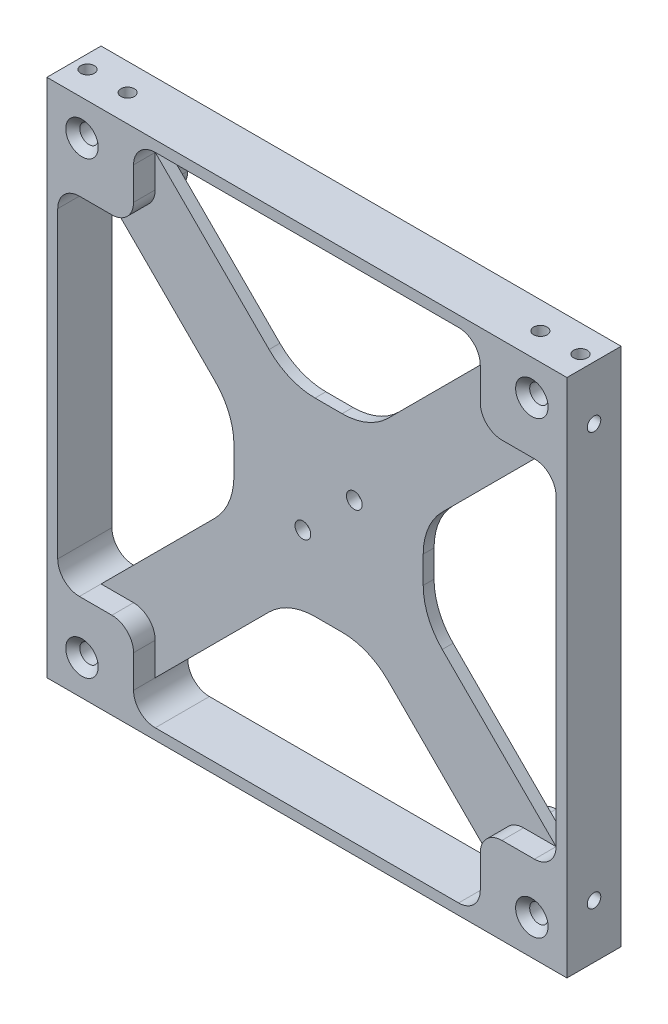
SolidWorks part; units mm, degrees
material "7075-T6 (SN)"
ref_plane "Front Plane" through (0, 0, 0) normal (0, 0, 1) x (1, 0, 0)
ref_plane "Top Plane" through (0, 0, 0) normal (0, 1, 0) x (1, 0, 0)
ref_plane "Right Plane" through (0, 0, 0) normal (1, 0, 0) x (0, 0, -1)
sketch "Construction Lines" plane through (0, 0, 0) normal (0, 0, 1) x (1, 0, 0)
  line L0 (0, 0) -> (0, -14.7163) construction
  line L1 (0, 0) -> (23.9312, 0) construction
sketch "Sketch3" plane through (0, 0, 0) normal (0, 0, 1) x (1, 0, 0)
  line L0 (0, 48) -> (48, 48)
  line L1 (0, 200000) -> (0, -200014.7163) construction
  line L2 (48, 48) -> (48, 0)
  line L3 (-200000, 0) -> (200023.9312, 0) construction
  line L4 (0, 46) -> (28, 46)
  line L5 (46, 28) -> (46, 0)
  line L6 (0, 48) -> (0, 46)
  line L7 (48, 0) -> (46, 0)
  line L8 (32, 42) -> (32, 36)
  line L9 (36, 32) -> (42, 32)
  line L11 (0, 46) -> (46, 46) construction
  line L12 (46, 46) -> (46, 0) construction
  arc A0 (28, 46) -> (32, 42) centre (28, 42) cw
  arc A1 (32, 36) -> (36, 32) centre (36, 36) ccw
  arc A2 (46, 28) -> (42, 32) centre (42, 28) ccw
  dimension "D6" = 4
  dimension "D1" = 48
  dimension "D2" = 48
  dimension "D4" = 16
  dimension "D5" = 16
  dimension "D3" = 2
extrude "BottomLayer" add sketch "Sketch3" along normal blind 4
sketch "TopHolePosition" plane through (0, 0, 4) normal (0, 0, 1) x (1, 0, 0)
  line L0 (0, 0) -> (48, 48) construction
sketch "Sketch6" plane through (0, 0, 4) normal (0, 0, 1) x (1, 0, 0)
  line L0 (0, 17.4706) -> (0, 0)
  line L1 (0, 0) -> (17.4706, 0)
  line L3 (0, 17.4706) -> (2.5, 17.4706)
  line L4 (0, 0) -> (48, 48) construction
  line L6 (17.4706, 0) -> (17.4706, 2.5)
  line L7 (38, 48) -> (10.9853, 20.9853)
  line L8 (48, 38) -> (20.9853, 10.9853)
  line L15 (48, 48) -> (0, 48) construction
  line L16 (48, 0) -> (48, 48) construction
  line L17 (38, 48) -> (48, 48)
  line L18 (48, 48) -> (48, 38)
  arc A1 (20.9853, 10.9853) -> (17.4706, 2.5) centre (29.4706, 2.5) ccw
  arc A2 (10.9853, 20.9853) -> (2.5, 17.4706) centre (2.5, 29.4706) cw
  dimension "D1" = 2.5
  dimension "D2" = 2.5
  dimension "D4" = 12
extrude "MiddleLayer" add sketch "Sketch6" along normal blind 2
sketch "Sketch10" plane through (0, 0, 6) normal (0, 0, 1) x (1, 0, 0)
  line L8 (48, 48) -> (0, 48)
  line L9 (48, 0) -> (48, 48)
  line L10 (46, 0) -> (48, 0)
  line L11 (46, 28) -> (46, 0)
  line L12 (36, 32) -> (42, 32)
  line L13 (32, 42) -> (32, 36)
  line L14 (0, 46) -> (28, 46)
  line L15 (0, 48) -> (0, 46)
  line L16 (48, 48) -> (0, 48)
  line L17 (48, 0) -> (48, 48)
  line L18 (46, 0) -> (48, 0)
  line L19 (46, 28) -> (46, 0)
  line L20 (36, 32) -> (42, 32)
  line L21 (32, 42) -> (32, 36)
  line L22 (0, 46) -> (28, 46)
  line L23 (0, 48) -> (0, 46)
  arc A3 (46, 28) -> (42, 32) centre (42, 28) ccw
  arc A4 (46, 28) -> (42, 32) centre (42, 28) ccw
  arc A5 (32, 36) -> (36, 32) centre (36, 36) ccw
  arc A6 (32, 36) -> (36, 32) centre (36, 36) ccw
  arc A7 (32, 42) -> (28, 46) centre (28, 42) ccw
  arc A8 (32, 42) -> (28, 46) centre (28, 42) ccw
  dimension "D1" = 0
extrude "FillUpLayer" add sketch "Sketch10" against normal blind 2
sketch "Sketch11" plane through (0, 0, 6) normal (0, 0, 1) x (1, 0, 0)
  line L8 (48, 48) -> (0, 48)
  line L9 (48, 0) -> (48, 48)
  line L10 (46, 0) -> (48, 0)
  line L11 (46, 28) -> (46, 0)
  line L12 (36, 32) -> (42, 32)
  line L13 (32, 42) -> (32, 36)
  line L14 (0, 46) -> (28, 46)
  line L15 (0, 48) -> (0, 46)
  line L16 (48, 48) -> (0, 48)
  line L17 (48, 0) -> (48, 48)
  line L18 (46, 0) -> (48, 0)
  line L19 (46, 28) -> (46, 0)
  line L20 (36, 32) -> (42, 32)
  line L21 (32, 42) -> (32, 36)
  line L22 (0, 46) -> (28, 46)
  line L23 (0, 48) -> (0, 46)
  arc A3 (46, 28) -> (42, 32) centre (42, 28) ccw
  arc A4 (46, 28) -> (42, 32) centre (42, 28) ccw
  arc A5 (32, 36) -> (36, 32) centre (36, 36) ccw
  arc A6 (32, 36) -> (36, 32) centre (36, 36) ccw
  arc A7 (32, 42) -> (28, 46) centre (28, 42) ccw
  arc A8 (32, 42) -> (28, 46) centre (28, 42) ccw
  dimension "D1" = 0
extrude "TopLayer" add sketch "Sketch11" along normal blind 4
sketch "HolePosition" plane through (0, 0, 10) normal (0, 0, 1) x (1, 0, 0)
  line L0 (0, 41.525) -> (41.525, 41.525) construction
  line L1 (0, 200000) -> (0, -200014.7163) construction
  line L2 (0, 0) -> (48, 48) construction
  line L3 (41.525, 41.525) -> (41.525, 0) construction
  line L4 (-200000, 0) -> (200023.9312, 0) construction
  dimension "D1" = 41.525
hole_wizard "M3 Clearance Hole1" positions "Sketch13" profile "Sketch14" hole size "M3" standard "ISO" end condition through all
sketch "Sketch13" plane through (0, 0, 10) normal (0, 0, 1) x (1, 0, 0)
  point P0 (41.525, 41.525)
sketch "Sketch14" plane through (41.525, 41.525, 10) normal (1, 0, 0) x (0, -1, 0)
  line L0 (0, 0) -> (0, 10)
  line L1 (0, 10) -> (1.7, 10)
  line L2 (1.7, 10) -> (1.7, 1.3)
  line L3 (1.7, 1.3) -> (3, 0)
  line L5 (3, 0) -> (0, 0)
  line L6 (-1.7, 1.3) -> (-3, 0) construction
  line L11 (0, -6.35) -> (0, 107.95) construction
  dimension "Thru Hole Dia." = 3.4
  dimension "Thru Hole Depth" = 10
  dimension "Near C'Sink Dia." = 6
  dimension "Near C'Sink Angle" = 90
ref_axis "Axis1" through (0, 0, -0.5) along (0, 0, 1)
sketch "M2HolePositions" plane through (0, 0, 6) normal (0, 0, 1) x (1, 0, 0)
  line L0 (0, 0) -> (48, 48) construction
  line L1 (0, 200000) -> (0, -200014.7163) construction
  line L2 (0, 0) -> (6.9513, -6.9513) construction
  line L3 (-200000, 0) -> (200023.9312, 0) construction
  line L4 (0, 4.75) -> (4.75, 4.75) construction
  line L5 (4.75, 4.75) -> (4.75, 0) construction
  dimension "D1" = 45
  dimension "D3" = 4.75
hole_wizard "M2.5 Clearance Hole1" positions "Sketch24" profile "Sketch25" hole size "M2.5" standard "ISO" end condition through all
sketch "Sketch24" plane through (0, 0, 6) normal (0, 0, 1) x (1, 0, 0)
  point P0 (4.75, 4.75)
sketch "Sketch25" plane through (4.75, 4.75, 6) normal (1, 0, 0) x (0, -1, 0)
  line L0 (0, 0) -> (0, 6)
  line L1 (0, 6) -> (1.45, 6)
  line L2 (1.45, 6) -> (1.45, 0)
  line L5 (1.45, 0) -> (0, 0)
  line L11 (0, -6.35) -> (0, 107.95) construction
  dimension "Thru Hole Dia." = 2.9
  dimension "Thru Hole Depth" = 6
pattern_circular "CirPattern1" count 4 every 90 about axis through (0, 0, -0.5) along (0, 0, 1) of "TopLayer", "FillUpLayer", "MiddleLayer", "BottomLayer", "M3 Clearance Hole1"
sketch "SidePlate Hole ZY" plane through (48, 0, 0) normal (1, 0, 0) x (0, 0, -1)
  line L0 (-5, 48) -> (-5, -48) construction
  line L1 (-10, 48) -> (0, 48) construction
  line L2 (-10, -48) -> (0, -48) construction
  line L3 (-10, 38.1) -> (-5, 38.1) construction
  line L4 (-10, -48) -> (-10, 48) construction
  dimension "D1" = 9.9
sketch "SidePlate&RailHole ZX" plane through (0, 48, 0) normal (0, 1, 0) x (1, 0, 0)
  line L0 (48, -5) -> (-48, -5) construction
  line L1 (-48, -10) -> (-48, 0) construction
  line L2 (45.5, -10) -> (45.5, -5) construction
  line L5 (48, -10) -> (-48, -10) construction
  line L7 (38.1, -10) -> (38.1, -5) construction
  line L8 (48, -10) -> (48, 0) construction
  dimension "D1" = 2.5
  dimension "D2" = 9.9
hole_wizard "Tap Drill M3 Side Plate" positions "Sketch20" profile "Sketch21" hole size "M3" standard "ISO"
sketch "Sketch20" plane through (48, 0, 0) normal (1, 0, 0) x (0, 0, -1)
  point P0 (-5, 38.1)
sketch "Sketch21" plane through (48, 38.1, 5) normal (0, 1, 0) x (0, 0, -1)
  line L0 (0, 0) -> (0, 5.7511)
  line L1 (0, 5.7511) -> (1.25, 5)
  line L2 (1.25, 5) -> (1.25, 0)
  line L5 (1.25, 0) -> (0, 0)
  line L10 (0, 5.7511) -> (-1.25, 5) construction
  line L11 (0, -6.35) -> (0, 107.95) construction
  dimension "Hole Dia." = 2.5
  dimension "Hole Depth" = 5
  dimension "Drill Angle" = 118
ref_plane "MirrorPlaneForM2.5" through (0, 0, 0) normal (-0.7071, -0.7071, 0) x (0.7071, -0.7071, 0)
mirror "Camera Holes" about plane through (0, 0, 0) normal (-0.7071, -0.7071, 0) of "M2.5 Clearance Hole1"
hole_wizard "Tap Drill M3 Side Plate " positions "Sketch26" profile "Sketch27" hole size "M3" standard "ISO"
sketch "Sketch26" plane through (0, 48, 0) normal (0, 1, 0) x (1, 0, 0)
  point P0 (38.1, -5)
sketch "Sketch27" plane through (38.1, 48, 5) normal (1, 0, 0) x (0, 0, 1)
  line L0 (0, 0) -> (0, 5.7511)
  line L1 (0, 5.7511) -> (1.25, 5)
  line L2 (1.25, 5) -> (1.25, 0)
  line L5 (1.25, 0) -> (0, 0)
  line L10 (0, 5.7511) -> (-1.25, 5) construction
  line L11 (0, -6.35) -> (0, 107.95) construction
  dimension "Hole Dia." = 2.5
  dimension "Hole Depth" = 5
  dimension "Drill Angle" = 118
hole_wizard "Tap Drill M3 Rail" positions "Sketch28" profile "Sketch29" hole size "M3" standard "ISO"
sketch "Sketch28" plane through (0, 48, 0) normal (0, 1, 0) x (1, 0, 0)
  point P0 (45.5, -5)
sketch "Sketch29" plane through (45.5, 48, 5) normal (1, 0, 0) x (0, 0, 1)
  line L0 (0, 0) -> (0, 5.7511)
  line L1 (0, 5.7511) -> (1.25, 5)
  line L2 (1.25, 5) -> (1.25, 0)
  line L5 (1.25, 0) -> (0, 0)
  line L10 (0, 5.7511) -> (-1.25, 5) construction
  line L11 (0, -6.35) -> (0, 107.95) construction
  dimension "Hole Dia." = 2.5
  dimension "Hole Depth" = 5
  dimension "Drill Angle" = 118
mirror "SidePlate and Rail Holes 1" about plane through (0, 0, 0) normal (1, 0, 0) of "Tap Drill M3 Side Plate", "Tap Drill M3 Rail", "Tap Drill M3 Side Plate "
mirror "Side Plate and Rail Holes 2" about plane through (0, 0, 0) normal (0, 1, 0) of "SidePlate and Rail Holes 1"
sketch "Sketch30" plane through (0, 0, 0) normal (0, 0, -1) x (-1, 0, 0)
  circle A0 centre (-41.525, 41.525) radius 3.25
  point P0 (-41.525, 41.525)
extrude "Cut-Extrude1" cut sketch "Sketch30" against normal blind 3.4
pattern_circular "CirPattern2" count 4 over 360 about axis through (0, 0, -0.5) along (0, 0, 1) of "Cut-Extrude1"
